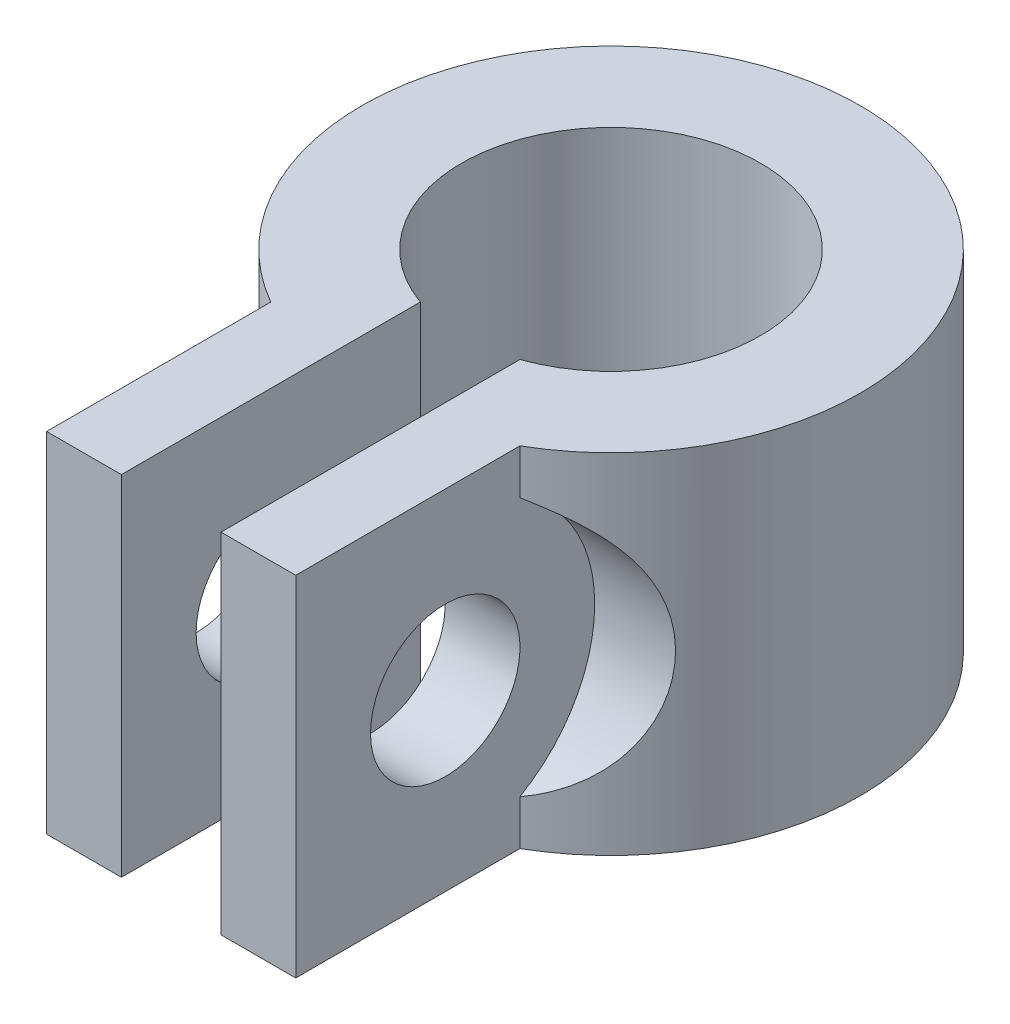
SolidWorks part; units mm, degrees
ref_plane "Front Plane" through (0, 0, 0) normal (0, 0, 1) x (1, 0, 0)
ref_plane "Top Plane" through (0, 0, 0) normal (0, 1, 0) x (1, 0, 0)
ref_plane "Right Plane" through (0, 0, 0) normal (1, 0, 0) x (0, 0, -1)
sketch "Sketch1" plane through (0, 0, 0) normal (0, 1, 0) x (1, 0, 0)
  circle A0 centre (0, 0) radius 3
  circle A1 centre (0, 0) radius 5
  dimension "D1" = 6
  dimension "D2" = 2
extrude "Boss-Extrude1" add sketch "Sketch1" along normal blind 7
sketch "Sketch2" plane through (0, 7, 0) normal (0, 1, 0) x (1, 0, 0)
  line L0 (0, -3.85) -> (0, 3.85) construction
  line L1 (1, -6.8411) -> (-1, -6.8411)
  line L2 (1, -6.8411) -> (1, -1.0103)
  line L3 (1, -1.0103) -> (-1, -1.0103)
  line L4 (-1, -6.8411) -> (-1, -1.0103)
  line L5 (1, -6.8411) -> (-1, -1.0103) construction
  line L6 (1, -1.0103) -> (-1, -6.8411) construction
  point P0 (0, -3.9257)
  dimension "D1" = 2
extrude "Cut-Extrude1" cut sketch "Sketch2" against normal blind 8
sketch "Sketch3" plane through (-1, 0, 0) normal (1, 0, 0) x (0, 0, -1)
  line L1 (-2.8284, 7) -> (-8.8284, 7)
  line L2 (-2.8284, 7) -> (-2.8284, 0)
  line L3 (-2.8284, 0) -> (-8.8284, 0)
  line L4 (-8.8284, 7) -> (-8.8284, 0)
  dimension "D1" = 6
extrude "Boss-Extrude2" add sketch "Sketch3" against normal blind 1.5
mirror "Mirror1" about plane through (0, 0, 0) normal (1, 0, 0) of "Boss-Extrude2"
sketch "Sketch4" plane through (1, 0, 0) normal (-1, 0, 0) x (0, 0, 1)
  line L0 (2.8284, 0) -> (8.8284, 7) construction
  line L1 (8.8284, 0) -> (2.8284, 7) construction
  circle A0 centre (5.8284, 3.5) radius 1.5
  dimension "D1" = 3
extrude "Cut-Extrude2" cut sketch "Sketch4" against normal through all and the other way through all
sketch "Sketch5" plane through (-2.5, 0, 0) normal (-1, 0, 0) x (0, 0, 1)
  line L0 (8.8284, 0) -> (2.8284, 7) construction
  circle A0 centre (5.8284, 3.5) radius 3
  dimension "D1" = 6
extrude "Cut-Extrude3" cut sketch "Sketch5" along normal through all contours A0
mirror "Mirror2" about plane through (0, 0, 0) normal (1, 0, 0) of "Cut-Extrude3"
